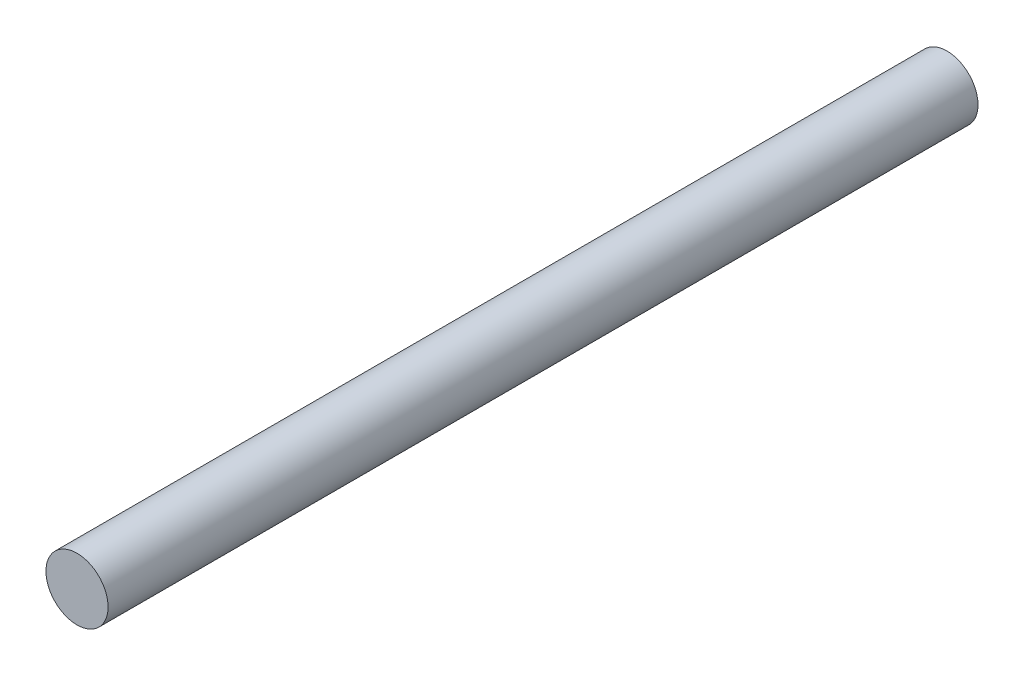
SolidWorks part; units mm, degrees
ref_plane "Front Plane" through (0, 0, 0) normal (0, 0, 1) x (1, 0, 0)
ref_plane "Top Plane" through (0, 0, 0) normal (0, 1, 0) x (1, 0, 0)
ref_plane "Right Plane" through (0, 0, 0) normal (1, 0, 0) x (0, 0, -1)
sketch "Sketch1" plane through (0, 0, 0) normal (0, 0, 1) x (1, 0, 0)
  circle A0 centre (0, 0) radius 12.7
  dimension "D1" = 25.4
extrude "Boss-Extrude1" add sketch "Sketch1" along normal blind 355.6
ref_axis "Axis1" through (0, 0, 355.6) along (0, 0, -1)
